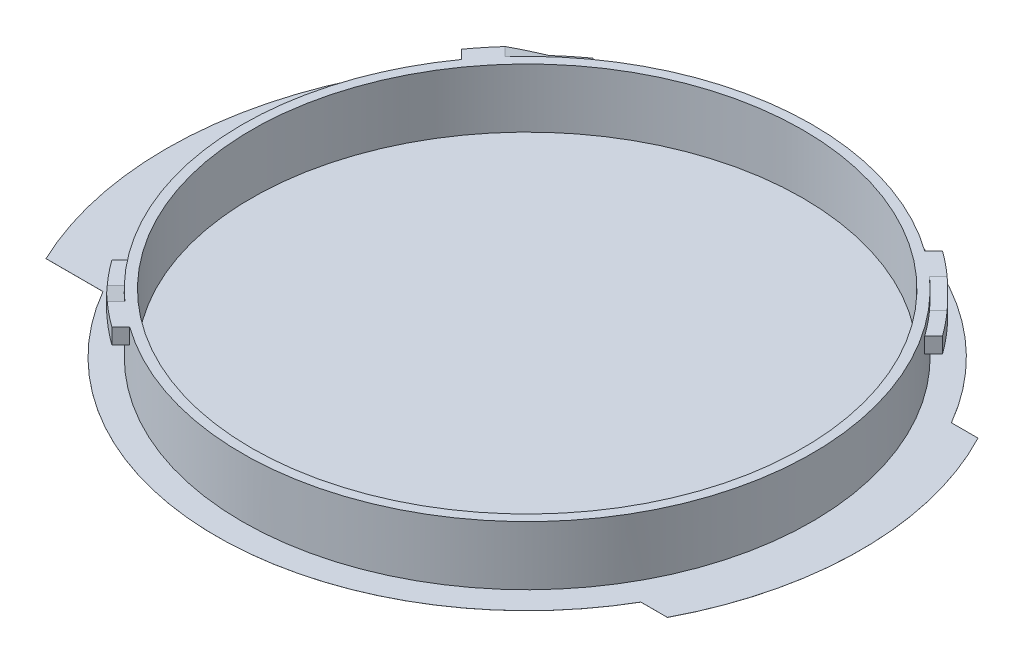
SolidWorks part; units mm, degrees
ref_plane "Płaszczyzna przednia" through (0, 0, 0) normal (0, 0, 1) x (1, 0, 0)
ref_plane "Płaszczyzna górna" through (0, 0, 0) normal (0, 1, 0) x (1, 0, 0)
ref_plane "Płaszczyzna prawa" through (0, 0, 0) normal (1, 0, 0) x (0, 0, -1)
sketch "Sketch1" plane through (0, 0, 0) normal (0, 1, 0) x (1, 0, 0)
  line L0 (-20.9896, 10) -> (-17.3205, 10)
  line L1 (-20.9896, -10) -> (-17.3205, -10)
  line L2 (17.3205, 10) -> (19.0329, 10)
  line L3 (17.3205, -10) -> (19.0329, -10)
  line L4 (0, 0) -> (-23.25, 0) construction
  arc A0 (17.3205, 10) -> (-17.3205, 10) centre (0, 0) ccw
  arc A1 (-20.9896, 10) -> (-20.9896, -10) centre (0, 0) ccw
  arc A3 (19.0329, -10) -> (19.0329, 10) centre (0, 0) ccw
  arc A4 (-17.3205, -10) -> (17.3205, -10) centre (0, 0) ccw
  dimension "D1" = 40
  dimension "D2" = 46.5
  dimension "D3" = 21.5
  dimension "D4" = 20
extrude "Boss-Extrude1" add sketch "Sketch1" along normal blind 1
sketch "Sketch2" plane through (0, 1, 0) normal (0, 1, 0) x (1, 0, 0)
  circle A0 centre (0, 0) radius 18.35
  circle A1 centre (0, 0) radius 17.75
  dimension "D1" = 36.7
  dimension "D2" = 35.5
extrude "Boss-Extrude2" add sketch "Sketch2" along normal blind 3.8
chamfer "Chamfer1" distance 4 angle 14 8 edges at (-19.155, 0, -10) (-23.25, 0, 0) (-19.155, 0, 10) (0, 0, 20) (18.1767, 0, 10) (21.5, 0, 0) (18.1767, 0, -10) (0, 0, -20) first distance on face at (-0.4633, 0, 0)
sketch "Sketch6" plane through (0, 1, 0) normal (0, 1, 0) x (1, 0, 0)
  line L0 (0, 0) -> (-10.6226, -10.6226) construction
  line L1 (0, 0) -> (-23.25, 0) construction
  dimension "D1" = 45
ref_plane "Plane3" through (-10.6226, 1, 10.6226) normal (-0.7071, 0, 0.7071) x (0.7071, 0, 0.7071)
sketch "Sketch3" plane through (0, 0, 0) normal (0, -1, 0) x (1, 0, 0)
  line L1 (-0.5, 5) -> (0.5, 5)
  line L2 (-0.5, 5) -> (-0.5, -5)
  line L3 (-0.5, -5) -> (0.5, -5)
  line L4 (0.5, 5) -> (0.5, -5)
  line L5 (-0.5, 5) -> (0.5, -5) construction
  line L6 (-0.5, -5) -> (0.5, 5) construction
  point P0 (0, 0)
  dimension "D1" = 1
  dimension "D2" = 10
extrude "Cut-Extrude1" cut sketch "Sketch3" against normal blind 0.5
ref_plane "Plane1" through (17.6616, 1, -17.6616) normal (-0.7071, 0, 0.7071) x (0.7071, 0, 0.7071)
sketch "Sketch4" plane through (17.6616, 1, -17.6616) normal (-0.7071, 0, 0.7071) x (0.7071, 0, 0.7071)
  line L0 (-3, 3.8) -> (-1, 3.8)
  line L1 (-1, 3.8) -> (1, 3.3)
  line L2 (1, 3.3) -> (3, 3.3)
  line L3 (3, 3.3) -> (3, 2.3)
  line L4 (3, 2.3) -> (1, 2.3)
  line L5 (1, 2.3) -> (-1, 2.8)
  line L6 (-1, 2.8) -> (-3, 2.8)
  line L7 (-3, 2.8) -> (-3, 3.8)
  line L8 (0, 3.55) -> (0, -1) construction
  line L9 (18.35, 3.8) -> (-18.35, 3.8) construction
  dimension "D1" = 6
  dimension "D2" = 1.5
  dimension "D3" = 2
  dimension "D4" = 2
  dimension "D5" = 2
  dimension "D6" = 2
  dimension "D7" = 1
extrude "Boss-Extrude3" add sketch "Sketch4" along normal up to next
pattern_circular "CirPattern1" count 3 every 90 about axis through (0, 4.8, 0) along (0, -1, 0) of "Boss-Extrude3" reverse direction yes
ref_plane "Plane2" through (0, 5, 0) normal (0, 1, 0) x (1, 0, 0)
sketch "Sketch5" plane through (0, 5, 0) normal (0, 1, 0) x (1, 0, 0)
  circle A0 centre (0, 0) radius 19.15
  circle A1 centre (0, 0) radius 34.2844
  dimension "D1" = 38.3
extrude "Cut-Extrude2" cut sketch "Sketch5" against normal blind 2
